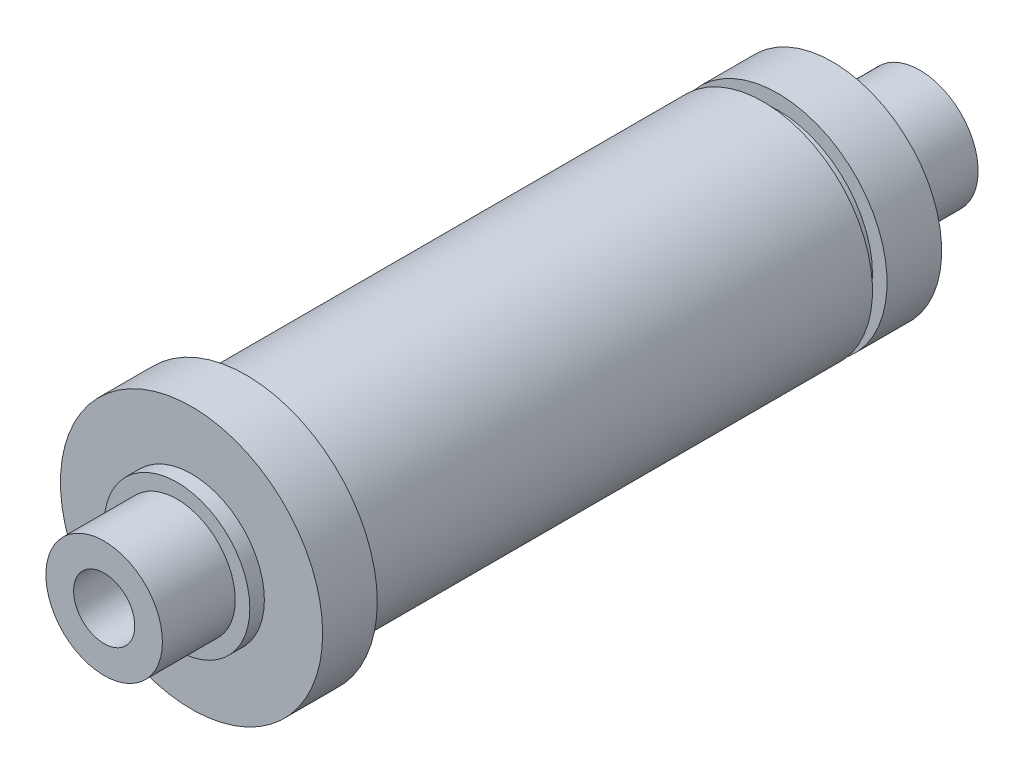
SolidWorks part; units mm, degrees
ref_plane "Спереди" through (0, 0, 0) normal (0, 0, 1) x (1, 0, 0)
ref_plane "Сверху" through (0, 0, 0) normal (0, 1, 0) x (1, 0, 0)
ref_plane "Справа" through (0, 0, 0) normal (1, 0, 0) x (0, 0, -1)
sketch "Эскиз1" plane through (0, 0, 0) normal (0, 0, 1) x (1, 0, 0)
  circle A0 centre (0, 0) radius 7.5
  dimension "D1" = 15
extrude "Бобышка-Вытянуть1" add sketch "Эскиз1" along normal blind 56
sketch "Эскиз2" plane through (0, 0, 56) normal (0, 0, 1) x (1, 0, 0)
  circle A0 centre (0, 0) radius 4
  circle A1 centre (0, 0) radius 7.5
  circle A2 centre (0, 0) radius 7.5 construction
  dimension "D1" = 8
extrude "Вырез-Вытянуть1" cut sketch "Эскиз2" against normal blind 6
sketch "Эскиз3" plane through (0, 0, 0) normal (0, 0, -1) x (-1, 0, 0)
  circle A0 centre (0, 0) radius 4
  circle A1 centre (0, 0) radius 7.5
  circle A2 centre (0, 0) radius 7.5 construction
  dimension "D1" = 8
extrude "Вырез-Вытянуть2" cut sketch "Эскиз3" against normal blind 6
ref_plane "Плоскость1" through (0, 0, 46.25) normal (0, 0, 1) x (1, 0, 0)
ref_plane "Плоскость2" through (0, 0, 10.75) normal (0, 0, -1) x (-1, 0, 0)
hole_wizard "Отверстие обработанное метчиком M5x0.81" positions "Эскиз7" profile "Эскиз6" tap size "M5x0.8" standard "Ansi Metric"
sketch "Эскиз7" plane through (0, 0, 0) normal (0, 0, -1) x (-1, 0, 0)
  point P0 (0, 0)
sketch "Эскиз6" plane through (0, 0, 0) normal (1, 0, 0) x (0, 1, 0)
  line L0 (0, 0) -> (0, 11.2618)
  line L1 (0, 11.2618) -> (2.1, 10)
  line L2 (2.1, 10) -> (2.1, 0)
  line L5 (2.1, 0) -> (0, 0)
  line L10 (0, 11.2618) -> (-2.1, 10) construction
  line L11 (0, -6.35) -> (0, 107.95) construction
  dimension "Диаметр сверла" = 4.2
  dimension "Глубина сверла" = 10
  dimension "Угол заточки сверла" = 118
cosmetic thread "Отверстие резьбы1" parameters "D1"=10, "D2"=5
hole_wizard "Отверстие обработанное метчиком M5x0.82" positions "Эскиз9" profile "Эскиз8" tap size "M5x0.8" standard "Ansi Metric"
sketch "Эскиз9" plane through (0, 0, 56) normal (0, 0, 1) x (1, 0, 0)
  point P0 (0, 0)
sketch "Эскиз8" plane through (0, 0, 56) normal (1, 0, 0) x (0, -1, 0)
  line L0 (0, 0) -> (0, 11.2618)
  line L1 (0, 11.2618) -> (2.1, 10)
  line L2 (2.1, 10) -> (2.1, 0)
  line L5 (2.1, 0) -> (0, 0)
  line L10 (0, 11.2618) -> (-2.1, 10) construction
  line L11 (0, -6.35) -> (0, 107.95) construction
  dimension "Диаметр сверла" = 4.2
  dimension "Глубина сверла" = 10
  dimension "Угол заточки сверла" = 118
cosmetic thread "Отверстие резьбы2" parameters "D1"=10, "D2"=5
sketch "Эскиз10" plane through (0, 0, 46.25) normal (0, 0, 1) x (1, 0, 0)
  circle A0 centre (0, 0) radius 9
  dimension "D2" = 18
sketch "Эскиз11" plane through (0, 0, 10.75) normal (0, 0, -1) x (-1, 0, 0)
  circle A0 centre (0, 0) radius 7.5
  circle A1 centre (0, 0) radius 6.5
  circle A2 centre (0, 0) radius 7.5 construction
  dimension "D1" = 13
extrude "Вырез-Вытянуть4" cut sketch "Эскиз11" along normal blind 1
sketch "Эскиз12" plane through (0, 0, 6) normal (0, 0, -1) x (-1, 0, 0)
  circle A0 centre (0, 0) radius 4
  circle A1 centre (0, 0) radius 5
  circle A2 centre (0, 0) radius 4 construction
  dimension "D1" = 10
extrude "Бобышка-Вытянуть2" add sketch "Эскиз12" along normal blind 1
sketch "Эскиз13" plane through (0, 0, 50) normal (0, 0, 1) x (1, 0, 0)
  circle A0 centre (0, 0) radius 4
  circle A1 centre (0, 0) radius 5
  circle A2 centre (0, 0) radius 4 construction
  dimension "D1" = 10
extrude "Бобышка-Вытянуть3" add sketch "Эскиз13" along normal blind 1
extrude "Бобышка-Вытянуть4" add sketch "Эскиз10" along normal up to surface (3.75 mm away) up to face at (7.5, 0, 50)
